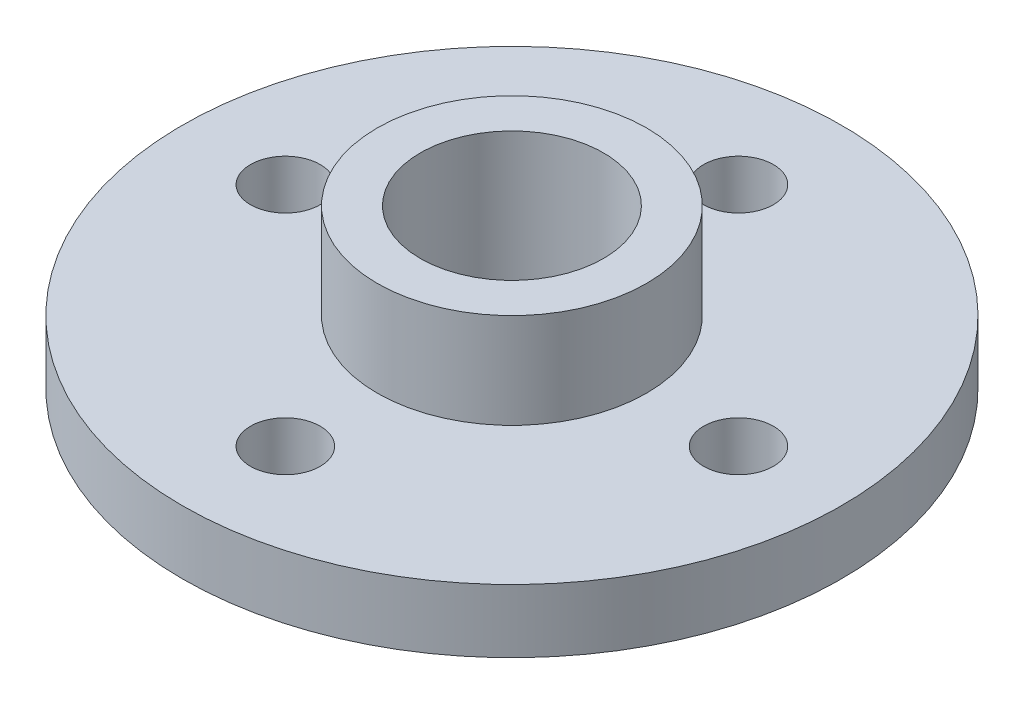
SolidWorks part; units mm, degrees
material "1060 Alloy"
ref_plane "Front Plane" through (0, 0, 0) normal (0, 0, 1) x (1, 0, 0)
ref_plane "Top Plane" through (0, 0, 0) normal (0, 1, 0) x (1, 0, 0)
ref_plane "Right Plane" through (0, 0, 0) normal (1, 0, 0) x (0, 0, -1)
sketch "Sketch2" plane through (0, 0, 0) normal (0, 1, 0) x (1, 0, 0)
  circle A0 centre (0, 0) radius 10.4
  dimension "D1" = 20.8
extrude "Boss-Extrude1" add sketch "Sketch2" along normal blind 2
sketch "Sketch3" plane through (0, 2, 0) normal (0, 1, 0) x (1, 0, 0)
  line L0 (0, 0) -> (0, 12.6294) construction
  line L1 (0, 0) -> (16.4383, 0) construction
  circle A1 centre (0, 7.15) radius 1
  circle A2 centre (7.15, 0) radius 1
  circle A3 centre (0, -7.15) radius 1
  circle A4 centre (-7.15, 0) radius 1
  dimension "D1" = 14.3
  dimension "D3" = 2
  dimension "D2" = 14.3
sketch "Sketch4" plane through (0, 2, 0) normal (0, 1, 0) x (1, 0, 0)
  circle A0 centre (0, 0) radius 4.25
  dimension "D1" = 8.5
extrude "Boss-Extrude2" add sketch "Sketch4" along normal blind 3
sketch "Sketch5" plane through (0, 5, 0) normal (0, 1, 0) x (1, 0, 0)
  circle A0 centre (0, 0) radius 1.5
  dimension "D1" = 3
extrude "Cut-Extrude2" cut sketch "Sketch5" against normal through all
sketch "Sketch6" plane through (0, 5, 0) normal (0, 1, 0) x (1, 0, 0)
  circle A0 centre (0, 0) radius 2.89
  dimension "D1" = 5.78
extrude "Cut-Extrude3" cut sketch "Sketch6" against normal blind 4.5
hole_wizard "M2 Clearance Hole1" positions "Sketch7" profile "Sketch8" hole size "M2" standard "ANSI Metric" end condition through all
sketch "Sketch7" plane through (0, 0, 0) normal (0, -1, 0) x (-1, 0, 0)
  point P0 (0, 7.15)
  point P3 (-7.15, 0)
  point P6 (0, -7.15)
  point P9 (7.15, 0)
sketch "Sketch8" plane through (0, 0, -7.15) normal (1, 0, 0) x (0, 0, -1)
  line L0 (0, 0) -> (0, 5)
  line L1 (0, 5) -> (1.1, 5)
  line L2 (1.1, 5) -> (1.1, 0.025)
  line L3 (1.1, 0.025) -> (1.125, 0)
  line L5 (1.125, 0) -> (0, 0)
  line L6 (-1.1, 0.025) -> (-1.125, 0) construction
  line L11 (0, -6.35) -> (0, 107.95) construction
  dimension "Thru Hole Dia." = 2.2
  dimension "Thru Hole Depth" = 5
  dimension "Near C'Sink Dia." = 2.25
  dimension "Near C'Sink Angle" = 90
